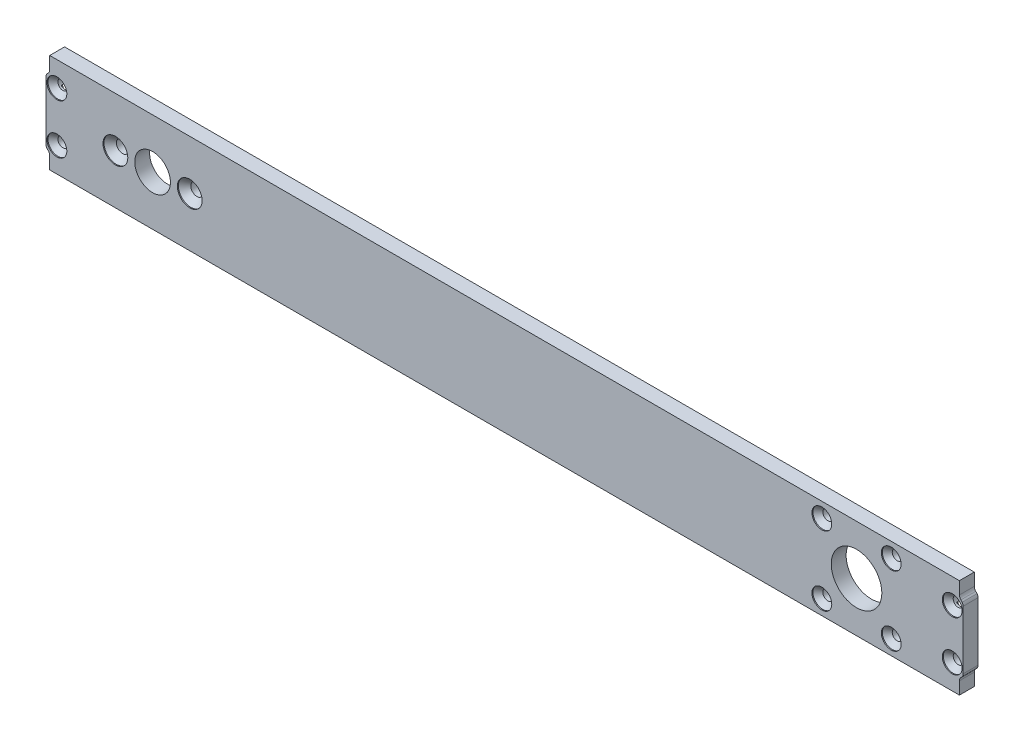
SolidWorks part; units mm, degrees
ref_plane "Front Plane" through (0, 0, 0) normal (0, 0, 1) x (1, 0, 0)
ref_plane "Top Plane" through (0, 0, 0) normal (0, 1, 0) x (1, 0, 0)
ref_plane "Right Plane" through (0, 0, 0) normal (1, 0, 0) x (0, 0, -1)
sketch "Sketch1" plane through (0, 0, 0) normal (0, 0, 1) x (1, 0, 0)
  line L1 (-92.5, 10) -> (92.5, 10)
  line L2 (-92.5, 10) -> (-92.5, -10)
  line L3 (-92.5, -10) -> (92.5, -10)
  line L4 (92.5, 10) -> (92.5, -10)
  line L5 (-92.5, 10) -> (92.5, -10) construction
  line L6 (-92.5, -10) -> (92.5, 10) construction
  point P0 (0, 0)
  dimension "D1" = 20
  dimension "D2" = 185
extrude "Base shape" add sketch "Sketch1" against normal blind 3
sketch "Sketch2" plane through (0, 0, 0) normal (0, 0, 1) x (1, 0, 0)
  line L0 (-81, 10) -> (-81, -10) construction
  line L1 (92.5, 10) -> (-92.5, 10) construction
  line L2 (-92.5, -10) -> (92.5, -10) construction
  line L3 (-92.5, 10) -> (-92.5, -10) construction
  line L4 (-92.5, 0) -> (92.5, 0) construction
  line L5 (92.5, -10) -> (92.5, 10) construction
  line L6 (-71, 10) -> (-71, -10) construction
  line L7 (0, 10) -> (0, -10) construction
  line L8 (71, 5.1) -> (92.5, 5.1) construction
  line L9 (-71, 3.6) -> (-92.5, 3.6) construction
  line L11 (78, -7) -> (64, -7)
  line L12 (78, -7) -> (78, 7)
  line L13 (78, 7) -> (64, 7)
  line L14 (64, -7) -> (64, 7)
  line L15 (78, -7) -> (64, 7) construction
  line L16 (78, 7) -> (64, -7) construction
  circle A0 centre (-71, 0) radius 10
  circle A1 centre (-78.5, 0) radius 1.25
  circle A2 centre (-63.5, 0) radius 1.25
  circle A3 centre (-71, 0) radius 3.6
  circle A4 centre (71, 0) radius 5.1
  circle A5 centre (64, 7) radius 1
  circle A6 centre (78, 7) radius 1
  circle A7 centre (78, -7) radius 1
  circle A8 centre (64, -7) radius 1
  dimension "D2" = 20
  dimension "D3" = 2.5
  dimension "D4" = 15
  dimension "D5" = 7.2
  dimension "D6" = 10.2
  dimension "D8" = 2
  dimension "D1" = 142
  dimension "D7" = 14
extrude "Motor cutouts" cut sketch "Sketch2" against normal up to next contours A5 | A6 | A7 | A8 | A1 | A2 | A3 | A4
sketch "Sketch5" plane through (0, 0, -3) normal (0, 0, -1) x (-1, 0, 0)
  line L0 (0, 10) -> (0, -10) construction
  line L3 (-92.5, 10) -> (92.5, 10) construction
  line L4 (92.5, -10) -> (-92.5, -10) construction
  line L5 (-60, -7) -> (60, -7) construction
  line L6 (-60, -6) -> (60, -6)
  line L7 (-60, -8) -> (60, -8)
  arc A0 (-60, -6) -> (-60, -8) centre (-60, -7) ccw
  arc A1 (60, -8) -> (60, -6) centre (60, -7) ccw
  point P8 (0, -7)
  dimension "D1" = 120
  dimension "D2" = 2
  dimension "D3" = 2
extrude "PCB slot" cut sketch "Sketch5" against normal blind 0.775
sketch "Sketch6" plane through (0, 0, 0) normal (0, 0, 1) x (1, 0, 0)
  line L0 (90.3, 10) -> (90.3, -10) construction
  line L1 (92.5, 10) -> (-92.5, 10) construction
  line L2 (-92.5, -10) -> (92.5, -10) construction
  line L3 (92.5, -10) -> (92.5, 10) construction
  line L4 (92.5, 0) -> (-92.5, 0) construction
  line L5 (-92.5, 10) -> (-92.5, -10) construction
  line L6 (0, 10) -> (0, -10) construction
  circle A0 centre (90.3, 5) radius 1
  circle A2 centre (90.3, -5) radius 1
  circle A3 centre (-90.3, -5) radius 1
  circle A5 centre (-90.3, 5) radius 1
  dimension "D2" = 2
  dimension "D1" = 2.2
  dimension "D3" = 10
extrude "End plate holes" cut sketch "Sketch6" against normal up to next
hole_wizard "M2.5 countersunks" positions "Sketch3" profile "Sketch4" countersink size "M2.5" standard "ANSI Metric" end condition through all
sketch "Sketch3" plane through (0, 0, 0) normal (0, 0, 1) x (1, 0, 0)
  point P0 (-78.5, 0)
  point P3 (-63.5, 0)
  point P29 (0, 0)
  point P30 (0, 0)
  point P31 (0, 0)
  point P32 (0, 0)
  point P33 (0, 0)
  point P34 (0, 0)
  point P35 (0, 0)
sketch "Sketch4" plane through (-78.5, 0, 0) normal (1, 0, 0) x (0, -1, 0)
  line L0 (0, 0) -> (0, 3)
  line L1 (0, 3) -> (1.25, 3)
  line L2 (1.25, 3) -> (1.25, 1.45)
  line L3 (1.25, 1.45) -> (2.5, 0.2)
  line L4 (2.5, 0.2) -> (2.5, 0)
  line L6 (2.5, 0) -> (0, 0)
  line L7 (-1.25, 1.45) -> (-2.5, 0.2) construction
  line L11 (0, -6.35) -> (0, 107.95) construction
  dimension "Thru Hole Dia." = 2.5
  dimension "Thru Hole Depth" = 3
  dimension "C'Sink Dia." = 5
  dimension "C'Sink Angle" = 90
  dimension "Head Clearance" = 0.2
hole_wizard "M2 countersunks" positions "Sketch10" profile "Sketch9" countersink size "M2" standard "ANSI Metric" end condition through all
sketch "Sketch10" plane through (0, 0, 0) normal (0, 0, 1) x (1, 0, 0)
  point P2 (90.3, 5)
  point P8 (90.3, -5)
  point P11 (-90.3, 5)
  point P17 (-90.3, -5)
  point P20 (78, -7)
  point P23 (64, -7)
  point P26 (64, 7)
  point P29 (78, 7)
sketch "Sketch9" plane through (90.3, 5, 0) normal (1, 0, 0) x (0, -1, 0)
  line L0 (0, 0) -> (0, 3)
  line L1 (0, 3) -> (1, 3)
  line L2 (1, 3) -> (1, 1.2)
  line L3 (1, 1.2) -> (2, 0.2)
  line L4 (2, 0.2) -> (2, 0)
  line L6 (2, 0) -> (0, 0)
  line L7 (-1, 1.2) -> (-2, 0.2) construction
  line L11 (0, -6.35) -> (0, 107.95) construction
  dimension "Thru Hole Dia." = 2
  dimension "Thru Hole Depth" = 3
  dimension "C'Sink Dia." = 4
  dimension "C'Sink Angle" = 90
  dimension "Head Clearance" = 0.2
sketch "Sketch12" plane through (0, 0, -3) normal (0, 0, -1) x (-1, 0, 0)
  line L0 (-92.5, 0) -> (92.5, 0) construction
  line L1 (-92.5, -10) -> (-92.5, 10) construction
  line L2 (92.5, 10) -> (92.5, -10) construction
  line L3 (-90.3, 5) -> (-90.3, -5) construction
  line L4 (-88.7, 4.05) -> (-91.9, 0.85) construction
  line L5 (-91.9, 4.05) -> (-88.7, 4.05)
  line L6 (-91.9, 4.05) -> (-91.9, -4.05)
  line L7 (-91.9, -4.05) -> (-88.7, -4.05)
  line L8 (-88.7, 4.05) -> (-88.7, -4.05)
  line L9 (-91.9, 4.05) -> (-88.7, -4.05) construction
  line L10 (-91.9, -4.05) -> (-88.7, 4.05) construction
  line L11 (0, 10) -> (0, -10) construction
  line L12 (-92.5, 10) -> (92.5, 10) construction
  line L13 (92.5, -10) -> (-92.5, -10) construction
  line L14 (91.9, -4.05) -> (88.7, -4.05)
  line L15 (91.9, 4.05) -> (88.7, 4.05)
  line L16 (91.9, 4.05) -> (91.9, -4.05)
  line L17 (88.7, 4.05) -> (88.7, -4.05)
  line L18 (-91.1929, 4.3429) -> (-89.4071, 4.3429)
  line L19 (-91.1929, -4.3429) -> (-89.4071, -4.3429)
  line L20 (91.1929, 4.3429) -> (89.4071, 4.3429)
  line L21 (91.1929, -4.3429) -> (89.4071, -4.3429)
  circle A0 centre (-89.4071, 3.3429) radius 1
  circle A1 centre (-91.1929, 3.3429) radius 1
  circle A2 centre (-89.4071, -3.3429) radius 1
  circle A3 centre (-91.1929, -3.3429) radius 1
  circle A4 centre (89.4071, -3.3429) radius 1
  circle A5 centre (91.1929, -3.3429) radius 1
  circle A6 centre (89.4071, 3.3429) radius 1
  circle A7 centre (91.1929, 3.3429) radius 1
  point P10 (-90.3, 0)
  circle M9 centre (-90.3, -5) radius 1
  circle M10 centre (90.3, -5) radius 1
  circle M11 centre (90.3, 5) radius 1
  circle M12 centre (-90.3, 5) radius 1
  dimension "D3" = 2
  dimension "D1" = 3.2
  dimension "D2" = 8.1
  dimension "D4" = 45
extrude "Tap slots" cut sketch "Sketch12" against normal blind 1.4 contours A1 L5 A0 L18 M12 | A3 L19 A2 L7 M9 | A7 L20 A6 L15 M11 | A5 L14 A4 L21 M10 | A1 | A0 | A2 | A3 | L6 L7 L8 L5 | A6 | A7 | A5 | A4 | L17 L14 L16 L15 region at (90.3, 4.2292, -3) region at (90.3, -4.2292, -3) region at (-90.3, -4.2292, -3) region at (-90.3, 4.2292, -3)
sketch "Sketch13" plane through (0, 0, 0) normal (0, 0, 1) x (1, 0, 0)
  line L0 (-92.5, -10) -> (92.5, -10) construction
  line L1 (-92.5, 10) -> (-91.75, 10)
  line L2 (-92.5, 10) -> (-92.5, -10)
  line L3 (-92.5, -10) -> (-91.75, -10)
  line L4 (-91.75, 10) -> (-91.75, -10)
  line L5 (-92.5, 0) -> (92.5, 0) construction
  line L6 (92.5, -10) -> (92.5, 10) construction
  line L7 (0, 10) -> (0, -10) construction
  line L8 (92.5, 10) -> (-92.5, 10) construction
  line L9 (92.5, -10) -> (91.75, -10)
  line L10 (91.75, 10) -> (91.75, -10)
  line L11 (92.5, 10) -> (91.75, 10)
  line L12 (92.5, 10) -> (92.5, -10)
  circle A0 centre (-90.3, 5) radius 2.5
  circle A1 centre (-90.3, -5) radius 2.5
  circle A2 centre (90.3, 5) radius 2.5
  circle A3 centre (90.3, -5) radius 2.5
  line M16 (92.5, -10) -> (92.5, 10)
  line M17 (92.5, 10) -> (-92.5, 10)
  line M18 (-92.5, 10) -> (-92.5, -10)
  line M19 (-92.5, -10) -> (92.5, -10)
  dimension "D2" = 5
  dimension "D1" = 0.75
extrude "Cut-Extrude3" cut sketch "Sketch13" against normal up to next contours A0 L4 M17 M18 | A1 L4 M18 M19 | L10 A2 M16 M17 | A3 L10 M16 M19 region at (-92.1406, 8.3301, 0) region at (92.1406, 8.3301, 0) region at (-92.1406, -8.3301, 0) region at (92.1406, -8.3301, 0)
fillet "Fillet1" radius 1 8 edges at (-91.75, -7.0365, -1.5) (-92.5, -6.1874, -1.5) (-92.5, 6.1874, -1.5) (-91.75, 7.0365, -1.5) (92.5, 6.1874, -1.5) (91.75, 7.0365, -1.5) (92.5, -6.1874, -1.5) (91.75, -7.0365, -1.5)
